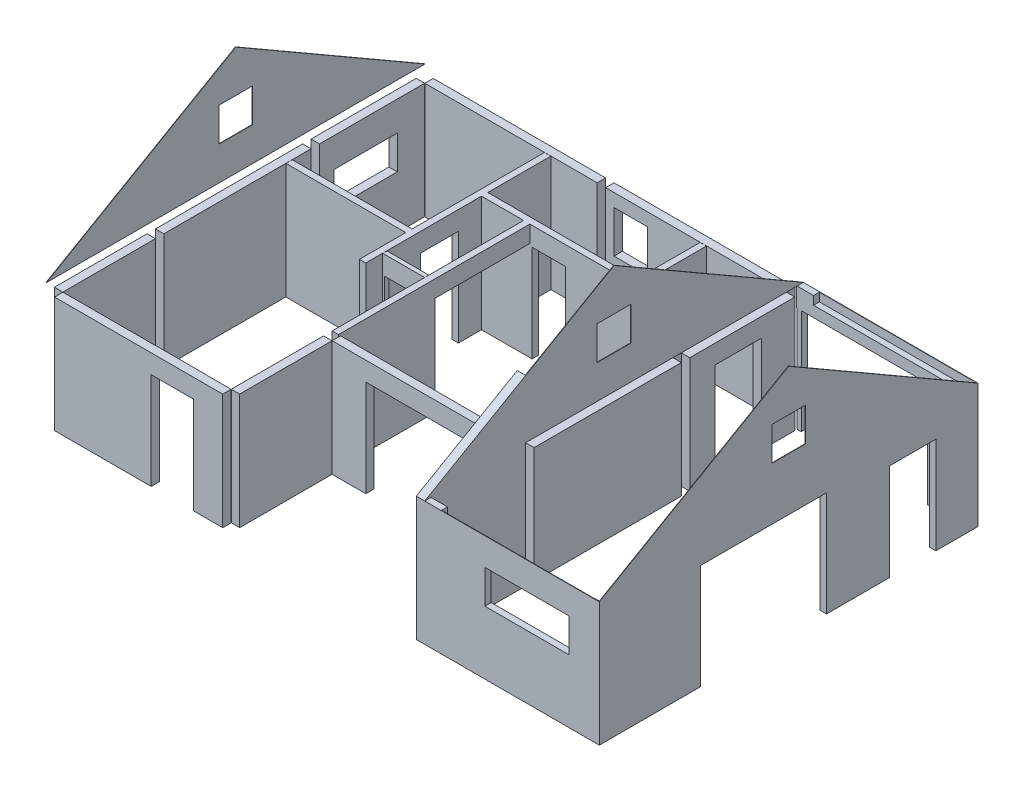
SolidWorks part; units mm, degrees
ref_plane "Спереди" through (0, 0, 0) normal (0, 0, 1) x (1, 0, 0)
ref_plane "Сверху" through (0, 0, 0) normal (0, 1, 0) x (1, 0, 0)
ref_plane "Справа" through (0, 0, 0) normal (1, 0, 0) x (0, 0, -1)
sketch "Эскиз1" plane through (0, 0, 0) normal (0, 1, 0) x (1, 0, 0)
  line L0 (9000, -6600) -> (4400, -6600) construction
  line L1 (0, 0) -> (9000, 0) construction
  line L2 (0, 0) -> (0, -8800) construction
  line L3 (0, -9000) -> (4400, -9000) construction
  line L4 (9000, 0) -> (9000, -6600) construction
  line L5 (4400, -6600) -> (4400, -9000) construction
  line L6 (8800, -203) -> (9000, -203)
  line L7 (203, 0) -> (4300, 0)
  line L8 (203, 0) -> (203, -200)
  line L9 (203, -200) -> (4300, -200)
  line L12 (0, -200) -> (0, -2700)
  line L14 (200, -200) -> (200, -2700)
  line L15 (203, -9000) -> (2500, -9000)
  line L16 (203, -9000) -> (203, -8800)
  line L17 (203, -8800) -> (2500, -8800)
  line L19 (4400, -8797) -> (4200, -8797)
  line L20 (4400, -8797) -> (4400, -6603)
  line L22 (4200, -8797) -> (4200, -6603)
  line L24 (9000, -203) -> (9000, -1000)
  line L26 (8800, -203) -> (8800, -1000)
  line L27 (8797, -6600) -> (7597, -6600)
  line L28 (8797, -6600) -> (8797, -6400)
  line L29 (8797, -6400) -> (7597, -6400)
  line L31 (2500, -8800) -> (2500, -9000)
  line L32 (3500, -8800) -> (3500, -9000)
  line L33 (3500, -8800) -> (4200, -8800)
  line L34 (3500, -9000) -> (4200, -9000)
  line L35 (5597, -6400) -> (5597, -6600)
  line L36 (7597, -6400) -> (7597, -6600)
  line L37 (5597, -6400) -> (4400, -6400)
  line L38 (5597, -6600) -> (4400, -6600)
  line L39 (8800, -1000) -> (9000, -1000)
  line L41 (8800, -2100) -> (9000, -2100)
  line L42 (8800, -2100) -> (8800, -2700)
  line L43 (9000, -2100) -> (9000, -2700)
  line L47 (4200, -6400) -> (4350, -6400)
  line L83 (4200, -6603) -> (4400, -6603)
  line L92 (4200, -4100) -> (4350, -4100)
  line L93 (4200, -4100) -> (4200, -6400)
  line L94 (4350, -4100) -> (4350, -6400)
  line L100 (200, -8800) -> (0, -8800)
  line L101 (4200, -8800) -> (4200, -9000)
  line L102 (4400, -6400) -> (4400, -6600)
  line L103 (8800, -6400) -> (9000, -6400)
  line L104 (0, -200) -> (200, -200)
  line L108 (0, -4500) -> (0, -6400)
  line L109 (200, -4500) -> (200, -6400)
  line L110 (8800, 0) -> (8800, -200)
  line L111 (4300, 0) -> (4300, -200)
  line L113 (4500, 0) -> (4500, -200)
  line L114 (4500, 0) -> (8800, 0)
  line L115 (4500, -200) -> (8800, -200)
  line L116 (0, -9000) -> (0, -8800) construction
  line L117 (-6170.9643, 0) -> (12200, 0) construction
  line L118 (0, 1882.3698) -> (0, -11726.3327) construction
  line L119 (-6170.9643, -4500) -> (10764.3505, -4500) construction
  line L120 (1000, -4500) -> (2250, -4500) construction
  line L121 (-6170.9643, -9000) -> (12200, -9000) construction
  line L122 (1000, -4500) -> (1000, -4600) construction
  line L123 (1000, -4600) -> (2250, -4600) construction
  line L124 (2250, -4500) -> (2250, -4600) construction
  line L125 (1000, -4500) -> (2250, -4600) construction
  line L126 (1000, -4600) -> (2250, -4500) construction
  line L131 (0, -2700) -> (200, -2700)
  line L132 (0, -2900) -> (0, -4500)
  line L137 (3050, -203) -> (3200, -203)
  line L138 (3050, -203) -> (3050, -2400)
  line L139 (3050, -2400) -> (3200, -2400)
  line L140 (3200, -203) -> (3200, -1700)
  line L141 (3050, -203) -> (3200, -2400) construction
  line L142 (3050, -2400) -> (3200, -203) construction
  line L143 (3050, -3300) -> (3200, -3300)
  line L144 (3050, -3300) -> (3050, -3350)
  line L145 (3050, -4600) -> (3200, -4600)
  line L146 (3200, -3300) -> (3200, -4600)
  line L147 (3050, -3300) -> (3200, -4600) construction
  line L148 (3050, -4600) -> (3200, -3300) construction
  line L149 (4150, -4100) -> (4197, -4100)
  line L150 (4150, -4100) -> (4150, -4200)
  line L151 (4150, -4200) -> (4197, -4200)
  line L152 (4197, -4100) -> (4197, -4200)
  line L153 (4150, -4100) -> (4197, -4200) construction
  line L154 (4150, -4200) -> (4197, -4100) construction
  line L155 (203, -3350) -> (3050, -3350)
  line L156 (203, -3350) -> (203, -3500)
  line L157 (203, -3500) -> (3050, -3500)
  line L159 (203, -3350) -> (3050, -3500) construction
  line L160 (203, -3500) -> (3050, -3350) construction
  line L161 (6400, -3500) -> (8800, -3500) construction
  line L162 (4400, 2182.3698) -> (4400, -11426.3327) construction
  line L163 (5200, -1700) -> (6750, -1700)
  line L164 (9000, 2182.3698) -> (9000, -11265.4622) construction
  line L165 (5200, -1700) -> (5200, -1850)
  line L166 (5200, -1850) -> (6900, -1850)
  line L167 (6900, -1700) -> (6900, -1850)
  line L168 (5200, -1700) -> (6900, -1850) construction
  line L169 (5200, -1850) -> (6900, -1700) construction
  line L170 (5800, -2800) -> (8797, -2800) construction
  line L171 (5800, -2800) -> (5800, -2900) construction
  line L172 (5800, -2900) -> (8797, -2900) construction
  line L173 (8797, -2800) -> (8797, -2900) construction
  line L174 (5800, -2800) -> (8797, -2900) construction
  line L175 (5800, -2900) -> (8797, -2800) construction
  line L176 (6750, -203) -> (6900, -203)
  line L177 (6750, -203) -> (6750, -1700)
  line L179 (6900, -203) -> (6900, -1700)
  line L180 (6750, -203) -> (6900, -1700) construction
  line L181 (6750, -1700) -> (6900, -203) construction
  line L186 (3200, -1700) -> (4400, -1700)
  line L188 (3200, -1850) -> (4400, -1850)
  line L189 (4400, -1700) -> (4400, -1850)
  line L190 (3200, -1700) -> (4400, -1850) construction
  line L191 (3200, -1850) -> (4400, -1700) construction
  line L192 (5800, -2900) -> (6400, -2900) construction
  line L193 (5800, -2900) -> (5800, -3500) construction
  line L194 (5800, -3500) -> (6400, -3500) construction
  line L195 (6400, -2900) -> (6400, -3500) construction
  line L196 (5800, -2900) -> (6400, -3500) construction
  line L197 (5800, -3500) -> (6400, -2900) construction
  line L198 (12200, 0) -> (12200, -9000) construction
  line L199 (5350, -4400) -> (5800, -3500) construction
  line L204 (3203, -4100) -> (3250, -4100)
  line L205 (3203, -4100) -> (3203, -4200)
  line L206 (3203, -4200) -> (3250, -4200)
  line L207 (3250, -4100) -> (3250, -4200)
  line L208 (3203, -4100) -> (3250, -4200) construction
  line L209 (3203, -4200) -> (3250, -4100) construction
  line L210 (4350, -4400) -> (5350, -4400) construction
  line L211 (4350, -4400) -> (4350, -6400) construction
  line L212 (4350, -6400) -> (5350, -6400) construction
  line L213 (5350, -4400) -> (5350, -6400) construction
  line L214 (4350, -4400) -> (5350, -6400) construction
  line L215 (4350, -6400) -> (5350, -4400) construction
  line L216 (3200, -1850) -> (3200, -2400)
  line L217 (0, -2900) -> (200, -2900)
  line L218 (200, -2900) -> (200, -4500)
  line L219 (0, -6400) -> (200, -6400)
  line L220 (0, -6600) -> (0, -8800)
  line L221 (0, -6600) -> (200, -6600)
  line L222 (200, -6600) -> (200, -8800)
  line L223 (3050, -3500) -> (3050, -4600)
  line L224 (8800, -2700) -> (9000, -2700)
  line L225 (8800, -2900) -> (8800, -6400)
  line L226 (8800, -2900) -> (9000, -2900)
  line L227 (9000, -2900) -> (9000, -6400)
  point P14 (3226.5, -4150)
  point P17 (7298.5, -2850)
  point P41 (1625, -4550)
  point P52 (3125, -1301.5)
  point P62 (3125, -3950)
  point P67 (4173.5, -4150)
  point P72 (1626.5, -3425)
  point P103 (3800, -1775)
  point P104 (6825, -951.5)
  point P105 (4150, -4150)
  point P108 (6050, -1775)
  point P120 (6750, -951.5)
  point P122 (6100, -3200)
  point P127 (4850, -5400)
  dimension "D2" = 6600
  dimension "D3" = 9000
  dimension "D4" = 200
  dimension "D5" = 3
  dimension "D6" = 3
  dimension "D7" = 3
  dimension "D8" = 9000
  dimension "D9" = 200
  dimension "D10" = 3
  dimension "D11" = 3
  dimension "D12" = 700
  dimension "D13" = 50
  dimension "D14" = 4500
  dimension "D15" = 4000
  dimension "D16" = 100
  dimension "D17" = 800
  dimension "D18" = 4400
  dimension "D19" = 4600
  dimension "D20" = 1000
  dimension "D21" = 800
  dimension "D22" = 2000
  dimension "D23" = 1200
  dimension "D24" = 1100
  dimension "D25" = 3
  dimension "D26" = 200
  dimension "D27" = 1000
  dimension "D29" = 200
  dimension "D30" = 4500
  dimension "D31" = 3
  dimension "D32" = 200
  dimension "D33" = 3
  dimension "D34" = 900
  dimension "D35" = 3
  dimension "D36" = 900
  dimension "D37" = 50
  dimension "D38" = 150
  dimension "D39" = 100
  dimension "D40" = 3
  dimension "D41" = 2850
  dimension "D42" = 3150
  dimension "D43" = 1250
  dimension "D44" = 200
  dimension "D46" = 3550
  dimension "D47" = 1500
  dimension "D48" = 800
  dimension "D49" = 1900
  dimension "D50" = 950
  dimension "D51" = 3
  dimension "D53" = 800
  dimension "D54" = 3
  dimension "D55" = 4450
  dimension "D56" = 3500
  dimension "D57" = 2400
  dimension "D58" = 3000
  dimension "D59" = 1400
  dimension "D60" = 2650
  dimension "D61" = 600
  dimension "D63" = 2900
  dimension "D64" = 2300
  dimension "D65" = 1247
  dimension "D66" = 3200
  dimension "D67" = 2000
  dimension "D68" = 1000
  dimension "D72" = 200
extrude "Бобышка-Вытянуть3" add sketch "Эскиз1" along normal blind 2750 contours L155 | L42 L103 L43 L41 | L26 L39 L24 L6 | L113 L115 L110 L114 | L216 L188 L189 L186 L140 L137 L138 L139 | L179 L176 L177 L163 L165 L166 L167 | L157 L223 L145 L146 L143 L144 L155 L156 | L108 L219 L109 L218 L217 L132 | L222 L221 L220 L100 | L144 L145 L146 L143 | L140 L139 L138 L137 | L27 L36 L29 L28 | L8 L9 L111 L7 | L14 L131 L12 L104 | L100 L108 L132 L217 L218 L109 | L47 L94 L92 L93 | L35 L38 L102 L37 | L171 L172 L173 L170 | L19 L22 L83 L20 | L32 L34 L101 L33 | L15 L31 L17 L16 | L122 L120 L124 L123 | L205 L204 L207 L206 | L150 L149 L152 L151 | L165 L163 L167 L166 | L103 L227 L226 L225 region at (8900, 0, 601.5) region at (8900, 0, 2400) region at (100, 0, 7700) region at (100, 0, 4650) region at (6650, 0, 100) region at (3125, 0, 228.7863) region at (3125, 0, 3332.668) region at (5975, 0, 1723.6698)
sketch "Эскиз2" plane through (0, 0, 0) normal (-1, 0, 0) x (0, 0, 1)
  line L2 (850, 1250) -> (2350, 1250)
  line L3 (850, 1250) -> (850, 2050)
  line L4 (850, 2050) -> (2350, 2050)
  line L5 (2350, 1250) -> (2350, 2050)
  line L7 (200, 0) -> (2700, 0) construction
  line L8 (3350, 2750) -> (3350, 0) construction
  dimension "D1" = 1500
  dimension "D2" = 800
  dimension "D3" = 1250
  dimension "D4" = 1000
extrude "Вырез-Вытянуть2" cut sketch "Эскиз2" against normal blind 250
sketch "Эскиз3" plane through (0, 0, 0) normal (0, 0, -1) x (-1, 0, 0)
  line L0 (-4500, 0) -> (-8800, 0) construction
  line L8 (-5500, 2440) -> (-4700, 2440)
  line L9 (-5500, 2440) -> (-5500, 1440)
  line L10 (-5500, 1440) -> (-4700, 1440)
  line L11 (-4700, 2440) -> (-4700, 1440)
  line L15 (-4500, 2750) -> (-4500, 0) construction
  dimension "D1" = 200
  dimension "D2" = 2440
  dimension "D3" = 800
  dimension "D4" = 1000
  dimension "D5" = 1440
extrude "Вырез-Вытянуть3" cut sketch "Эскиз3" against normal blind 593
sketch "Эскиз4" plane through (0, 2750, 0) normal (0, 1, 0) x (1, 0, 0)
  line L6 (3203, -4100) -> (3250, -4100) construction
  line L7 (3226.5, -4100) -> (4173.5, -4100)
  line L8 (3226.5, -4100) -> (3226.5, -4200)
  line L9 (3226.5, -4200) -> (4173.5, -4200)
  line L10 (4173.5, -4100) -> (4173.5, -4200)
  line L11 (4150, -4200) -> (4197, -4200) construction
  line L13 (3050, -2346.4504) -> (3200, -2346.4504)
  line L14 (3050, -2346.4504) -> (3050, -3325)
  line L15 (3050, -3325) -> (3200, -3325)
  line L16 (3200, -2346.4504) -> (3200, -3325)
  line L19 (4249.5007, -1700) -> (5402.0861, -1700)
  line L20 (4249.5007, -1700) -> (4249.5007, -1850)
  line L21 (4249.5007, -1850) -> (5402.0861, -1850)
  line L22 (5402.0861, -1700) -> (5402.0861, -1850)
  line L24 (5200, -1850) -> (6900, -1850) construction
  line L29 (3050, -203) -> (3050, -2400) construction
  line L30 (5597, -6400) -> (4400, -6400) construction
  line L31 (5423.0031, -6400) -> (7690.4362, -6400)
  line L32 (5423.0031, -6400) -> (5423.0031, -6600)
  line L33 (5423.0031, -6600) -> (7690.4362, -6600)
  line L34 (7690.4362, -6400) -> (7690.4362, -6600)
  line L35 (8797, -6600) -> (7597, -6600) construction
  line L36 (8800, -203) -> (8800, -1000) construction
  line L37 (8800, -900.8258) -> (9000, -900.8258)
  line L38 (8800, -900.8258) -> (8800, -2153.976)
  line L39 (8800, -2153.976) -> (9000, -2153.976)
  line L40 (9000, -900.8258) -> (9000, -2153.976)
  line L41 (9000, -2100) -> (9000, -2700) construction
  line L42 (3500, -9000) -> (4200, -9000) construction
  line L43 (2379.0159, -8797) -> (3597.5552, -8797)
  line L44 (2379.0159, -8797) -> (2379.0159, -9000)
  line L45 (2379.0159, -9000) -> (3597.5552, -9000)
  line L46 (3597.5552, -8797) -> (3597.5552, -9000)
  line L47 (3200, -1850) -> (3200, -2400) construction
  line L48 (3200, -1700) -> (4400, -1700) construction
extrude "Бобышка-Вытянуть4" add sketch "Эскиз4" against normal offset from surface (450 mm away) 2300 up to face at (8900, 0, 601.5)
ref_plane "Плоскость1" through (13000, 0, 0) normal (1, 0, 0) x (0, 0, -1)
sketch "Эскиз5" plane through (13000, 0, 0) normal (1, 0, 0) x (0, 0, -1)
  line L0 (-4500, 5721.2813) -> (-4500, -150) construction
  line L1 (-6600, -150) -> (0, -150) construction
  line L2 (-4500, 5548.0762) -> (-9000, 2950)
  line L3 (-9000, 2950) -> (-9000, 0)
  line L5 (0, 2950) -> (0, 0)
  line L6 (-4500, 5548.0762) -> (0, 2950)
  line L7 (-8800, 0) -> (-9000, 0) construction
  line L8 (-9000, 0) -> (-8750, 0) construction
  line L9 (-9000, 0) -> (0, 0)
extrude "Бобышка-Вытянуть5" add sketch "Эскиз5" along normal blind 150 separate body
sketch "Эскиз6" plane through (13000, 0, 0) normal (1, 0, 0) x (0, 0, -1)
  line L0 (-9000, 0) -> (0, 0) construction
  line L1 (-1000, 2300) -> (-2100, 2300)
  line L2 (-1000, 2300) -> (-1000, 0)
  line L3 (-1000, 0) -> (-2100, 0)
  line L4 (-2100, 2300) -> (-2100, 0)
  line L5 (0, 2494.3376) -> (50, 2494.3376) construction
  line L6 (-6600, -150) -> (-3600, -150)
  line L7 (-6600, -150) -> (-6600, 2494.3376)
  line L8 (-6600, 2494.3376) -> (-3600, 2494.3376)
  line L9 (-3600, -150) -> (-3600, 2494.3376)
  dimension "D1" = 3000
  dimension "D2" = 1100
extrude "Вырез-Вытянуть5" cut sketch "Эскиз6" along normal blind 670
sketch "Эскиз8" plane through (0, 0, 0) normal (-1, 0, 0) x (0, 0, 1)
  line L0 (4500, 5548.0762) -> (0, 2950)
  line L1 (0, 2950) -> (9000, 2950)
  line L2 (9000, 2950) -> (4500, 5548.0762)
  line L3 (4500, 5548.0762) -> (4500, 2950) construction
  line L4 (2350, 1250) -> (2350, 2050) construction
  line L5 (4100, 4550) -> (4900, 4550)
  line L6 (4100, 4550) -> (4100, 3750)
  line L7 (4100, 3750) -> (4900, 3750)
  line L8 (4900, 4550) -> (4900, 3750)
  dimension "D1" = 800
extrude "Бобышка-Вытянуть8" add sketch "Эскиз8" against normal blind 10 separate body
sketch "Эскиз9" plane through (9000, 0, 0) normal (1, 0, 0) x (0, 0, -1)
  line L0 (-6600, 0) -> (-6600, 2950)
  line L1 (-6600, 2750) -> (-6600, 0) construction
  line L2 (-6600, 2950) -> (0, 2950)
  line L3 (0, 2950) -> (-4500, 5548.0762)
  line L4 (-4500, 5548.0762) -> (-9000, 2950)
  line L5 (-9000, 2950) -> (-9000, 0)
  line L6 (-9000, 0) -> (-6600, 0)
extrude "Бобышка-Вытянуть9" add sketch "Эскиз9" against normal blind 200 separate body
sketch "Эскиз10" plane through (0, 0, 0) normal (0, -1, 0) x (1, 0, 0)
  line L0 (13000, 9000) -> (13000, 6600) construction
  line L1 (9000, 9000) -> (13000, 9000)
  line L2 (9000, 9000) -> (9000, 8850)
  line L3 (9000, 8850) -> (13000, 8850)
  line L4 (13000, 9000) -> (13000, 8850)
  line L5 (13150, 9000) -> (13000, 9000) construction
  line L6 (9000, 6600) -> (9000, 0) construction
  line L7 (13000, 0) -> (12100, 0)
  line L8 (13000, 0) -> (13000, 150)
  line L9 (13000, 150) -> (12100, 150)
  line L10 (12100, 0) -> (12100, 150)
  line L11 (9000, 150) -> (9100, 150)
  line L12 (9000, 150) -> (9000, 0)
  line L13 (9000, 0) -> (9100, 0)
  line L14 (9100, 150) -> (9100, 0)
extrude "Бобышка-Вытянуть10" add sketch "Эскиз10" against normal up to vertex (2950 mm away) up to point (9000, 2950, 9000)
sketch "Эскиз11" plane through (0, 0, 6400) normal (0, 0, -1) x (-1, 0, 0)
  line L1 (-7597, 2300) -> (-5200, 2300)
  line L2 (-7597, 2300) -> (-7597, -335.5255)
  line L3 (-7597, -335.5255) -> (-5200, -335.5255)
  line L4 (-5200, 2300) -> (-5200, -335.5255)
  line L6 (-2500, 2300) -> (-3500, 2300)
  line L7 (-2500, 2300) -> (-2500, -123.1481)
  line L8 (-2500, -123.1481) -> (-3500, -123.1481)
  line L9 (-3500, 2300) -> (-3500, -123.1481)
  line L11 (-10431.0972, 2300) -> (-12431.0972, 2300)
  line L12 (-10431.0972, 2300) -> (-10431.0972, 1500)
  line L13 (-10431.0972, 1500) -> (-12431.0972, 1500)
  line L14 (-12431.0972, 2300) -> (-12431.0972, 1500)
  dimension "D1" = 2000
  dimension "D2" = 800
  dimension "D3" = 2397
extrude "Вырез-Вытянуть6" cut sketch "Эскиз11" against normal blind 5123
sketch "Эскиз12" plane through (0, 0, 0) normal (-1, 0, 0) x (0, 0, 1)
  line L0 (2424.8711, 2950) -> (2424.8711, 4350) construction
  line L1 (0, 2950) -> (9000, 2950) construction
  line L2 (4500, 5548.0762) -> (0, 2950) construction
  line L3 (2424.8711, 4350) -> (3290.8965, 4850) construction
  line L4 (3290.8965, 4850) -> (5709.1035, 4850) construction
  line L5 (9000, 2950) -> (4500, 5548.0762) construction
  line L6 (5709.1035, 4850) -> (6575.1289, 4350) construction
  line L7 (6575.1289, 4350) -> (6575.1289, 2950) construction
  line L8 (4500, 5548.0762) -> (4500, 4850) construction
  dimension "D1" = 1900
  dimension "D2" = 2418.2069
  dimension "D3" = 1400
  dimension "D4" = 4150.2577
extrude "Вырез-Вытянуть7" cut sketch "Эскиз8<2>" against normal blind 16606 contours L5 L8 L7 L6
sketch "Эскиз8<2>" plane through (0, 0, 0) normal (-1, 0, 0) x (0, 0, 1) same geometry as "Эскиз8"
sketch "Эскиз13" plane through (0, 0, 0) normal (-1, 0, 0) x (0, 0, 1)
  line L0 (4500, 5548.0762) -> (0, 2950)
  line L1 (0, 2950) -> (0, 0)
  line L2 (0, 0) -> (9000, 0)
  line L3 (9000, 2950) -> (9000, 0) construction
  line L4 (4500, 5548.0762) -> (9000, 2950)
  line L5 (9000, 2950) -> (9000, 0)
  line L7 (4100, 4550) -> (4900, 4550)
  line L8 (4100, 4550) -> (4100, 3750)
  line L9 (4100, 3750) -> (4900, 3750)
  line L10 (4900, 4550) -> (4900, 3750)
  line L11 (850, 2050) -> (2350, 2050)
  line L12 (850, 2050) -> (850, 1250)
  line L13 (850, 1250) -> (2350, 1250)
  line L14 (2350, 2050) -> (2350, 1250)
sketch "Эскиз16" plane through (13150, 0, 0) normal (1, 0, 0) x (0, 0, -1)
  line L0 (-150, 2950) -> (-150, 0) construction
  line L1 (0, 2950) -> (-150, 2950)
  line L2 (0, 2950) -> (0, 2494.3376)
  line L3 (0, 2494.3376) -> (-150, 2494.3376)
  line L4 (-150, 2950) -> (-150, 2494.3376)
  line L5 (-3600, 2494.3376) -> (-6600, 2494.3376) construction
extrude "Бобышка-Вытянуть16" add sketch "Эскиз16" against normal blind 4160
sketch "Эскиз17" plane through (0, 0, 4100) normal (0, 0, -1) x (-1, 0, 0)
  line L0 (-4200, 2750) -> (-4200, 0) construction
  line L1 (-4350, 2750) -> (-4200, 2750)
  line L2 (-4350, 2750) -> (-4350, 2350)
  line L3 (-4350, 2350) -> (-4200, 2350)
  line L4 (-4200, 2750) -> (-4200, 2350)
  dimension "D1" = 400
extrude "Бобышка-Вытянуть17" add sketch "Эскиз17" along normal up to surface (2250 mm away) up to face at (4925, 1262.5, 1850)
sketch "Эскиз18" plane through (0, 2750, 0) normal (0, 1, 0) x (1, 0, 0)
  line L0 (9000, -4500) -> (9000, -9000) construction
  line L1 (8644.5298, 46.0605) -> (8990, 46.0605)
  line L2 (8644.5298, 46.0605) -> (8644.5298, -6600)
  line L3 (8644.5298, -6600) -> (8990, -6600)
  line L4 (8990, 46.0605) -> (8990, -6600)
  line L5 (8797, -6600) -> (4400, -6600) construction
  line L6 (13000, -9000) -> (9000, -9000) construction
  line L7 (9392.4652, -10) -> (13140, -10)
  line L8 (9392.4652, -10) -> (9392.4652, -8990)
  line L9 (9392.4652, -8990) -> (13140, -8990)
  line L10 (13140, -10) -> (13140, -8990)
  line L11 (13150, -4500) -> (13150, -9000) construction
  line L12 (9000, 0) -> (13000, 0) construction
  dimension "D1" = 10
  dimension "D2" = 10
  dimension "D3" = 10
  dimension "D4" = 10
extrude "Вырез-Вытянуть8" cut sketch "Эскиз18" along normal blind 5414
